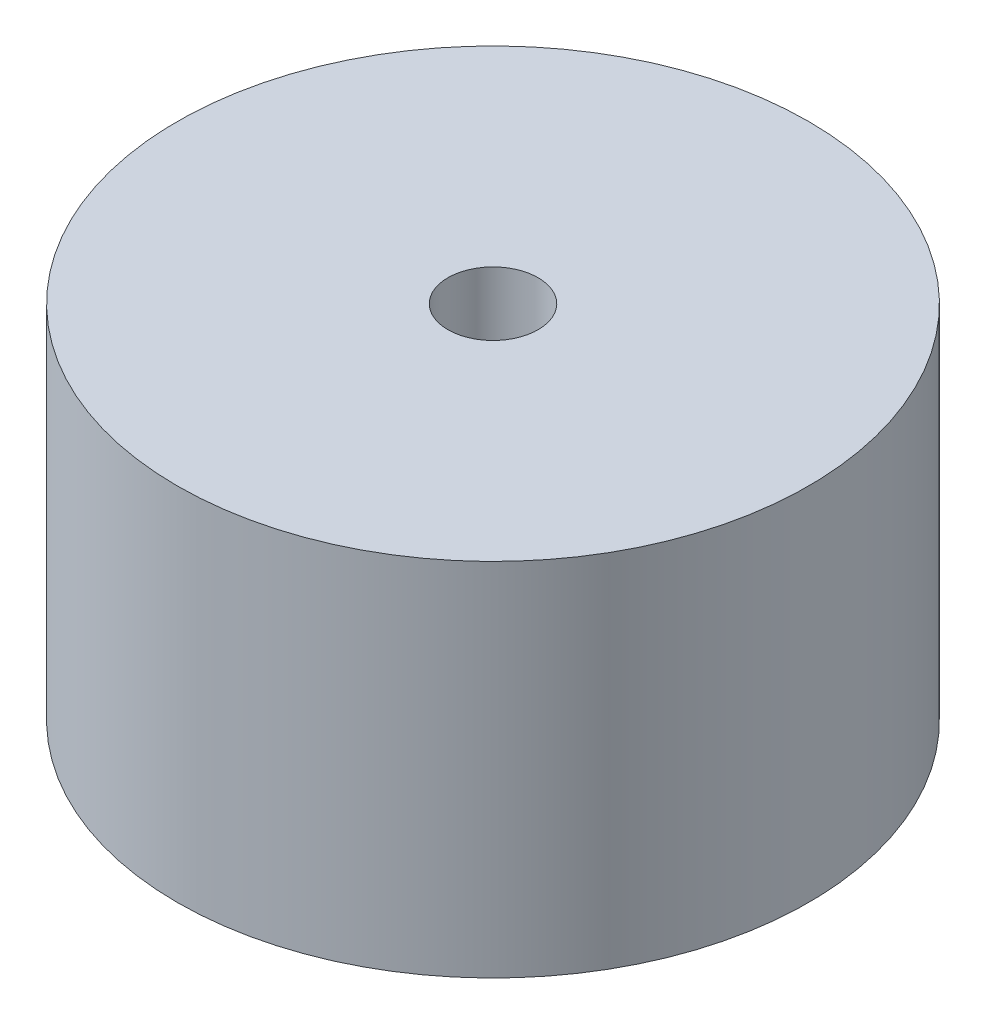
SolidWorks part; units mm, degrees
ref_plane "Front Plane" through (0, 0, 0) normal (0, 0, 1) x (1, 0, 0)
ref_plane "Top Plane" through (0, 0, 0) normal (0, 1, 0) x (1, 0, 0)
ref_plane "Right Plane" through (0, 0, 0) normal (1, 0, 0) x (0, 0, -1)
ref_axis "Axial" through (0, -26.67, 0) along (0, 1, 0)
ref_plane "Bottom Plane" through (0, -25.4, 0) normal (0, 1, 0) x (1, 0, 0)
sketch "Sketch1" plane through (0, 0, 0) normal (0, 1, 0) x (1, 0, 0)
  circle A0 centre (0, 0) radius 3.175
  circle A1 centre (0, 0) radius 22.225
  dimension "D1" = 44.45
  dimension "D2" = 6.35
extrude "Injector Head" add sketch "Sketch1" against normal blind 25.4
